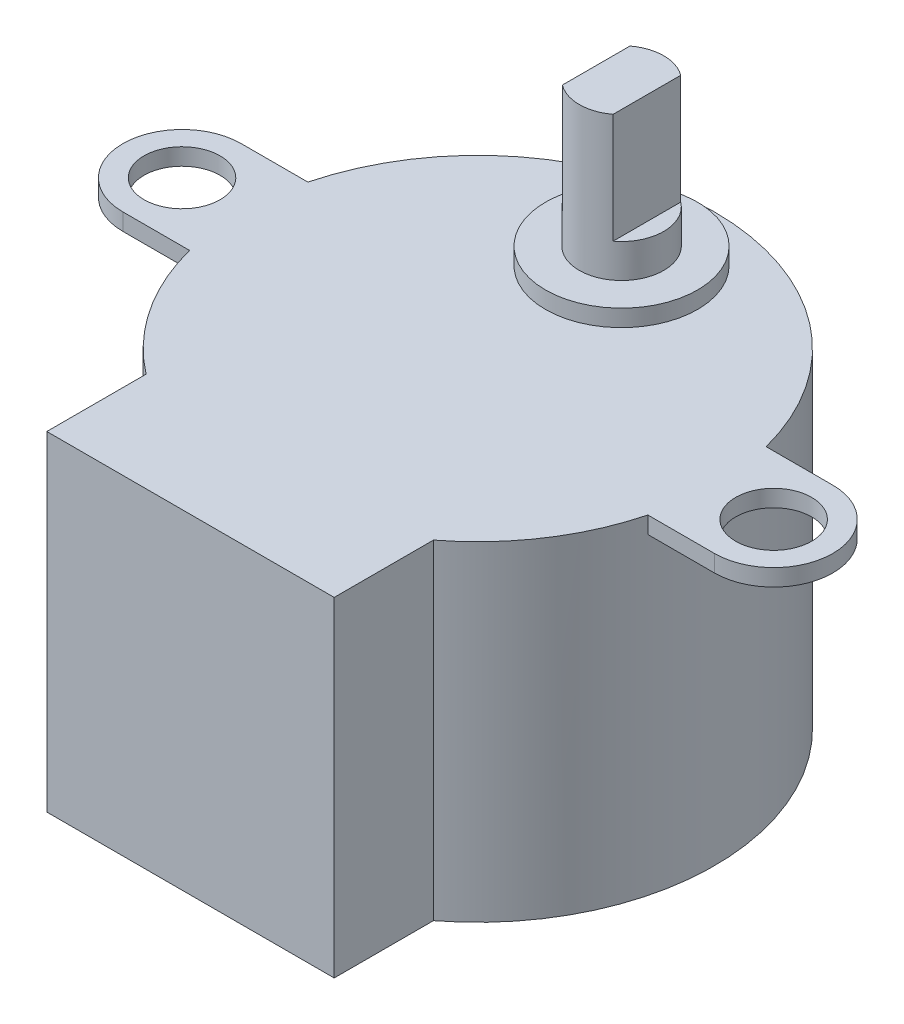
SolidWorks part; units mm, degrees
note: The reader was unsure of these and kept them because the rebuilt part matched: shared geometry of "Sketch2<3>", "Sketch2<4>", "Sketch2<5>", "Sketch2<6>".
ref_plane "Front Plane" through (0, 0, 0) normal (0, 0, 1) x (1, 0, 0)
ref_plane "Top Plane" through (0, 0, 0) normal (0, 1, 0) x (1, 0, 0)
ref_plane "Right Plane" through (0, 0, 0) normal (1, 0, 0) x (0, 0, -1)
sketch "Sketch2" plane through (0, 0, 0) normal (0, 1, 0) x (1, 0, 0)
  line L0 (0, 0) -> (0, 14) construction
  line L1 (8.5, -11) -> (8.5, -11.1243)
  line L2 (8.5, -17) -> (-8.5, -17)
  line L3 (8.5, -17) -> (8.5, -11)
  line L4 (8.5, -11) -> (-8.5, -11) construction
  line L5 (-8.5, -17) -> (-8.5, -11)
  line L6 (8.5, -17) -> (-8.5, -11) construction
  line L7 (8.5, -11) -> (-8.5, -17) construction
  line L8 (-8.5, -11) -> (-8.5, -11.1243)
  line L10 (17.5, -3.5) -> (-17.5, -3.5)
  line L11 (17.5, -3.5) -> (17.5, 3.5) construction
  line L12 (17.5, 3.5) -> (-17.5, 3.5)
  line L13 (-17.5, -3.5) -> (-17.5, 3.5) construction
  line L14 (17.5, -3.5) -> (-17.5, 3.5) construction
  line L15 (17.5, 3.5) -> (-17.5, -3.5) construction
  line L16 (1.5, 6.5) -> (-1.5, 6.5)
  line L17 (1.5, 6.5) -> (1.5, 10.5)
  line L18 (1.5, 10.5) -> (-1.5, 10.5)
  line L19 (-1.5, 6.5) -> (-1.5, 10.5)
  line L20 (1.5, 6.5) -> (-1.5, 10.5) construction
  line L21 (1.5, 10.5) -> (-1.5, 6.5) construction
  circle A0 centre (0, 0) radius 14
  circle A1 centre (0, 8.5) radius 4.5
  circle A2 centre (0, 8.5) radius 2.5
  circle A3 centre (-17.5, 0) radius 3.5
  circle A4 centre (17.5, 0) radius 3.5
  circle A5 centre (-17.5, 0) radius 2.25
  circle A6 centre (17.5, 0) radius 2.25
  point P4 (0, -14)
  dimension "D1" = 28
  dimension "D4" = 9
  dimension "D6" = 5
  dimension "D7" = 4.5
  dimension "D8" = 7
  dimension "D2" = 31
  dimension "D3" = 17
  dimension "D5" = 5.5
  dimension "D9" = 3
extrude "Boss-Extrude1" add sketch "Sketch2" along normal blind 19.5 contours A0 L10 | A0 L8 L5 L2 L3 L1 | L10 A0 L12 | L12 A0 A1 | A1 A2 | A2 | L19 L16 L17 L18 | L18 A2 | L19 A2 | L16 A2
extrude "Boss-Extrude2" add sketch "Sketch2<3>" against normal blind 1 from surface at 19.5 contours A3 L10 A0 L12 | A3 A5 | A4 L12 A0 L10 | A4 A6 | A4 L12 A0 | A3 A0 L12
sketch "Sketch2<3>" plane through (0, 0, 0) normal (0, 1, 0) x (1, 0, 0) same geometry as "Sketch2"
extrude "Boss-Extrude3" add sketch "Sketch2<4>" along normal blind 1 from surface at 19.5 contours A1 A2 | A2 | L19 A2 | L18 A2 | L19 L16 L17 L18 | L16 A2 starting at face at (0, 19.5, 3.8831)
sketch "Sketch2<4>" plane through (0, 0, 0) normal (0, 1, 0) x (1, 0, 0) same geometry as "Sketch2"
extrude "Boss-Extrude4" add sketch "Sketch2<5>" along normal blind 2 from surface at 20.5 contours L16 A2 | L19 L16 L17 L18 | L17 A2 | L19 A2 | L18 A2 starting at face at (0, 20.5, -4)
sketch "Sketch2<5>" plane through (0, 0, 0) normal (0, 1, 0) x (1, 0, 0) same geometry as "Sketch2"
extrude "Boss-Extrude5" add sketch "Sketch2<6>" along normal blind 6.5 from surface contours L16 A2 | L19 L16 L17 L18 | L18 A2
sketch "Sketch2<6>" plane through (0, 0, 0) normal (0, 1, 0) x (1, 0, 0) same geometry as "Sketch2"
